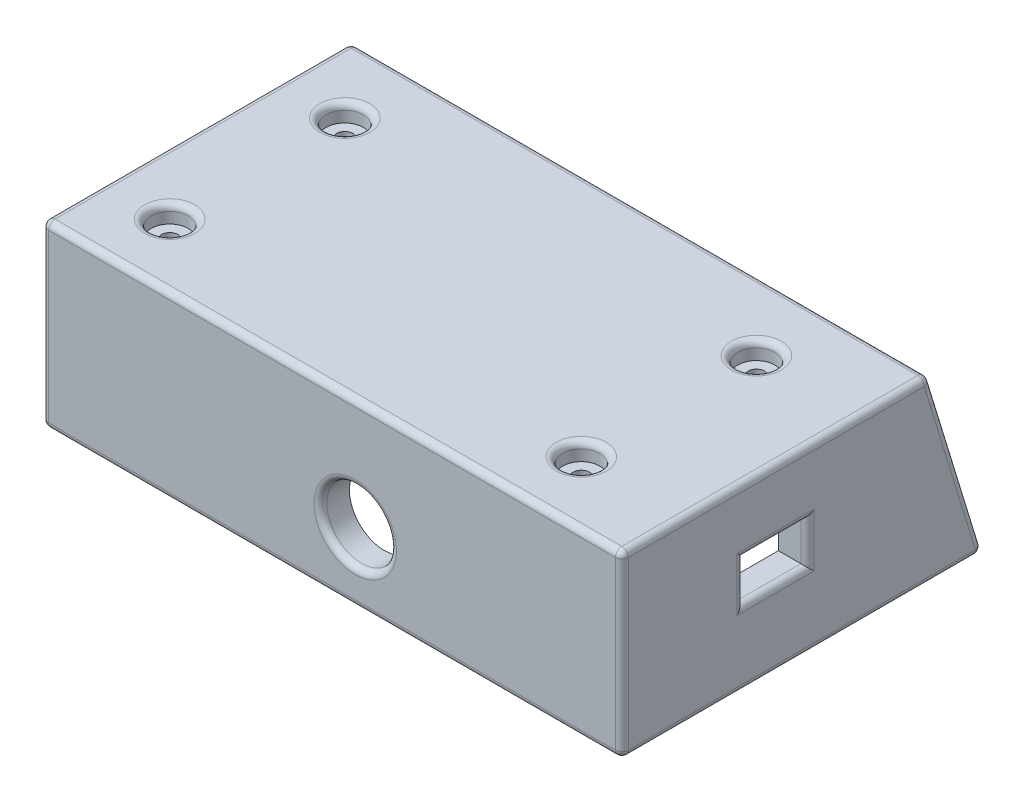
SolidWorks part; units mm, degrees
ref_plane "前基準面" through (0, 0, 0) normal (0, 0, 1) x (1, 0, 0)
ref_plane "上基準面" through (0, 0, 0) normal (0, 1, 0) x (1, 0, 0)
ref_plane "右基準面" through (0, 0, 0) normal (1, 0, 0) x (0, 0, -1)
sketch "草圖1" plane through (0, 0, 0) normal (0, 1, 0) x (1, 0, 0)
  line L1 (0, 0) -> (10, 0)
  line L2 (0, 0) -> (0, 5.3)
  line L3 (0, 5.3) -> (10, 5.3)
  line L4 (10, 0) -> (10, 5.3)
  dimension "D1" = 10
  dimension "D2" = 5.3
extrude "填料-伸長1" add sketch "草圖1" along normal blind 2.8
sketch "草圖3" plane through (0, 0, 0) normal (0, -1, 0) x (1, 0, 0)
  line L1 (9.5, -4.8) -> (0.5, -4.8)
  line L2 (9.5, -4.8) -> (9.5, -0.5)
  line L3 (9.5, -0.5) -> (0.5, -0.5)
  line L4 (0.5, -4.8) -> (0.5, -0.5)
extrude "除料-伸長1" cut sketch "草圖3" against normal blind 2.5
sketch "草圖4" plane through (0, 2.8, 0) normal (0, 1, 0) x (1, 0, 0)
  circle A3 centre (1.1, 1.1) radius 0.14
  circle A4 centre (1.1, 4.12) radius 0.14
  circle A6 centre (8.2, 1.1) radius 0.14
  circle A7 centre (8.2, 4.12) radius 0.14
extrude "除料-伸長2" cut sketch "草圖4" against normal up to surface (0.3 mm away) up to face at (5, 2.5, -2.65)
sketch "草圖5" plane through (10, 0, 0) normal (1, 0, 0) x (0, 0, -1)
  line L1 (3.2, 1.9969) -> (2.1003, 1.9969)
  line L2 (3.2, 1.9969) -> (3.2, 1.2962)
  line L3 (3.2, 1.2962) -> (2.1003, 1.2962)
  line L4 (2.1003, 1.9969) -> (2.1003, 1.2962)
  dimension "D1" = 0.7006
  dimension "D2" = 1.0997
extrude "除料-伸長3" cut sketch "草圖5" against normal up to next
sketch "草圖7" plane through (0, 0, -5.3) normal (0, 0, -1) x (-1, 0, 0)
  line L1 (-8, 0.3) -> (-5, 0.3)
  line L2 (-8, 0.3) -> (-8, 0.8)
  line L3 (-8, 0.8) -> (-5, 0.8)
  line L4 (-5, 0.3) -> (-5, 0.8)
extrude "除料-伸長4" cut sketch "草圖7" against normal up to next and the other way blind 10 contours L2 L1 L4 L3
sketch "草圖8" plane through (0, 2.8, 0) normal (0, 1, 0) x (1, 0, 0)
  line L1 (10, 0) -> (0, 0)
  line L2 (10, 0) -> (10, 5.3)
  line L3 (10, 5.3) -> (0, 5.3)
  line L4 (0, 0) -> (0, 5.3)
  circle A0 centre (8.2, 1.1) radius 0.32
  circle A1 centre (8.2, 4.12) radius 0.32
  circle A2 centre (1.1, 4.12) radius 0.32
  circle A3 centre (1.1, 1.1) radius 0.32
extrude "填料-伸長4" add sketch "草圖8" along normal blind 0.3
sketch "草圖9" plane through (0, 0, 0) normal (-1, 0, 0) x (0, 0, 1)
  line L0 (-5.3, 0) -> (-6.2489, 0)
  line L1 (-6.2489, 0) -> (-5.3, 3.1)
  line L2 (-5.3, 3.1) -> (-5.3, 0)
extrude "填料-伸長5" add sketch "草圖9" against normal up to surface (10 mm away) up to face at (10, 1.6466, -2.6501)
sketch "草圖10" plane through (0, 0, -4.8) normal (0, 0, 1) x (1, 0, 0)
  line L1 (5, 0.8) -> (8, 0.8)
  line L2 (5, 0.8) -> (5, 0.3)
  line L3 (5, 0.3) -> (8, 0.3)
  line L4 (8, 0.8) -> (8, 0.3)
extrude "除料-伸長5" cut sketch "草圖10" against normal up to next
sketch "草圖11" plane through (0, 0, 0) normal (0, 0, 1) x (1, 0, 0)
  circle A0 centre (5.4, 1.2) radius 0.6
extrude "除料-伸長6" cut sketch "草圖11" against normal up to next
scale "縮放比例1" bodies to scale 112 scale about centroid uniform scaling yes scale factor 10
fillet "圓角1" radius 1.11 4 edges at (-44.4554, -1.0608, -29.374) (-44.4554, 14.4392, 1.8703) (-44.4554, -1.0608, 28.3703) (-44.4554, -16.5608, -2.874)
fillet "圓角2" radius 1.11 8 edges at (55.5446, -1.0608, 28.3703) (55.5446, 14.4392, 1.8703) (55.5446, -1.0608, -29.374) (55.5446, -16.5608, -2.874) (55.5446, -0.0952, 7.3677) (55.5446, -3.5984, 1.8691) (55.5446, -0.0952, -3.6294) (55.5446, 3.408, 1.8691)
fillet "圓角3" radius 1.11 7 edges at (-44.1302, 14.1141, 28.0452) (55.2195, 14.1141, 28.0452) (-44.1302, -16.2357, 28.0452) (55.2195, -16.2357, 28.0452) (5.5446, 14.4392, 28.3703) (5.5446, -16.5608, 28.3703) (15.5446, -4.5608, 28.3703)
fillet "圓角4" radius 1.11 7 edges at (55.2195, 14.1141, -24.3892) (-44.1302, 14.1141, -24.3892) (-33.4554, 14.4392, 20.5703) (37.5446, 14.4392, -9.6297) (5.5446, 14.4392, -24.6297) (37.5446, 14.4392, 20.5703) (-33.4554, 14.4392, -9.6297)
fillet "圓角5" radius 1.11 7 edges at (55.2195, -16.2357, -33.6788) (-44.1302, -16.2357, -33.6788) (5.5446, -16.5608, -34.1183) (20.5446, -8.5608, -31.6696) (35.5446, -11.0608, -32.4348) (20.5446, -13.5608, -33.2001) (5.5446, -11.0608, -32.4348)
